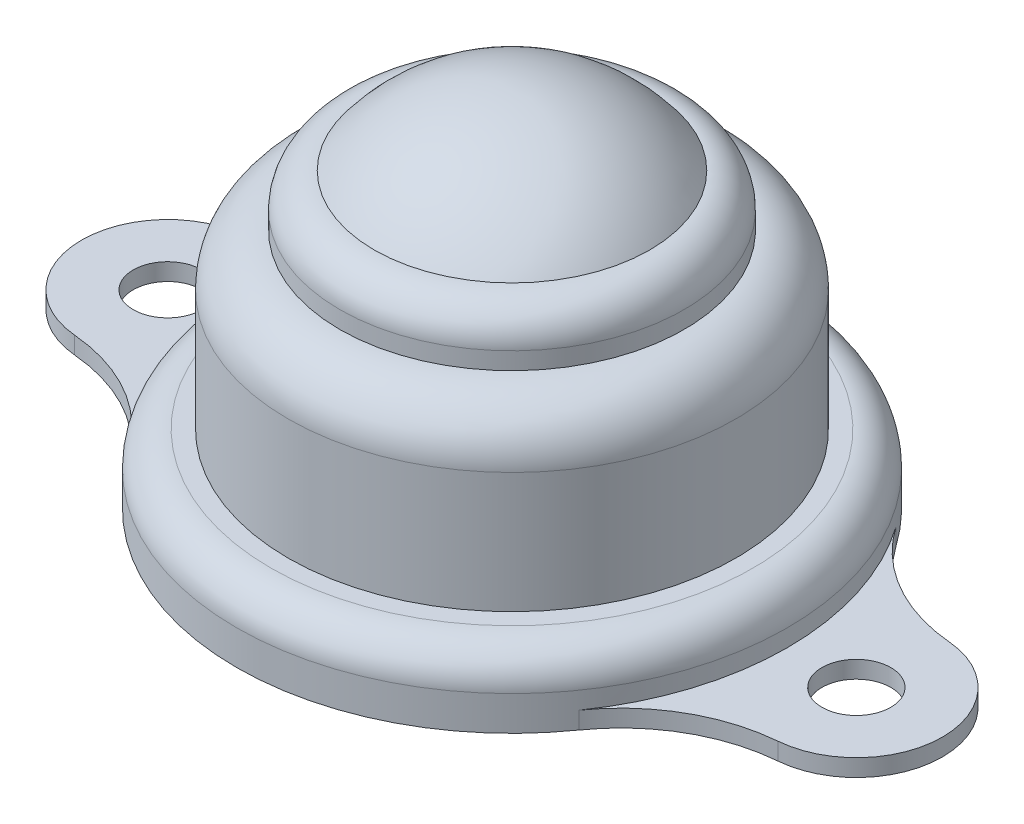
SolidWorks part; units mm, degrees
ref_plane "Front Plane" through (0, 0, 0) normal (0, 0, 1) x (1, 0, 0)
ref_plane "Top Plane" through (0, 0, 0) normal (0, 1, 0) x (1, 0, 0)
ref_plane "Right Plane" through (0, 0, 0) normal (1, 0, 0) x (0, 0, -1)
sketch "Sketch1" plane through (0, 0, 0) normal (0, 1, 0) x (1, 0, 0)
  line L0 (0, 0) -> (0, 10)
  circle A0 centre (-20, 0) radius 2
  circle A1 centre (20, 0) radius 2
  arc A2 (-20.425, 4.9819) -> (-20.425, -4.9819) centre (-20, 0) ccw
  arc A3 (20.425, -4.9819) -> (20.425, 4.9819) centre (20, 0) ccw
  circle A4 centre (0, 0) radius 10
  arc A5 (-13.0923, -9.1974) -> (13.0923, -9.1974) centre (0, 0) ccw
  arc A6 (13.0923, 9.1974) -> (-13.0923, 9.1974) centre (0, 0) ccw
  arc A7 (20.425, -4.9819) -> (13.0923, -9.1974) centre (21.275, -14.9457) ccw
  arc A8 (20.425, 4.9819) -> (13.0923, 9.1974) centre (21.275, 14.9457) cw
  arc A9 (-20.425, -4.9819) -> (-13.0923, -9.1974) centre (-21.275, -14.9457) cw
  arc A10 (-20.425, 4.9819) -> (-13.0923, 9.1974) centre (-21.275, 14.9457) ccw
  point P15 (15.775, 2.6738)
  dimension "D3" = 4
  dimension "D4" = 4
  dimension "D6" = 10
  dimension "D7" = 10
  dimension "D8" = 20
  dimension "D9" = 32
  dimension "D10" = 10
  dimension "D1" = 40
  dimension "D2" = 20
  dimension "D5" = 0
  dimension "D11" = 10
extrude "Boss-Extrude1" add sketch "Sketch1" along normal blind 1 contours A10 A2 A9 A5 A7 A3 A8 A6 A4 A1 A0 | A4 region at (-15.9952, 0, -5.7616) region at (-6.8711, 0, 6.8711)
sketch "Sketch2" plane through (0, 1, 0) normal (0, 1, 0) x (1, 0, 0)
  circle A0 centre (0, 0) radius 16
  circle A1 centre (0, 0) radius 13
  dimension "D1" = 32
  dimension "D2" = 26
extrude "Boss-Extrude2" add sketch "Sketch2" along normal blind 3 contours A0 | A1
fillet "Fillet2" radius 2 1 edges at (0, 4, 16)
ref_plane "Plane1" through (0, 4, 0) normal (0, 1, 0) x (1, 0, 0)
sketch "Sketch3" plane through (0, 4, 0) normal (0, 1, 0) x (1, 0, 0)
  circle A0 centre (0, 0) radius 13
  circle A1 centre (0, 0) radius 10
  dimension "D1" = 20
  dimension "D2" = 26
extrude "Boss-Extrude3" add sketch "Sketch3" along normal blind 10 separate body
sketch "Sketch4" plane through (0, 14, 0) normal (0, 1, 0) x (1, 0, 0)
  circle A0 centre (0, 0) radius 10
  circle A1 centre (0, 0) radius 8
  dimension "D1" = 20
  dimension "D2" = 16
extrude "Boss-Extrude4" add sketch "Sketch4" along normal blind 3 separate body
fillet "Fillet3" radius 2 1 edges at (0, 17, 10)
fillet "Fillet4" radius 3 1 edges at (0, 14, 13)
sketch "Sketch5" plane through (0, 0, 0) normal (0, 0, 1) x (1, 0, 0)
  line L0 (-13, 11) -> (-13, 4) construction
  line L2 (13, 4) -> (13, 11) construction
  line L3 (0, 1) -> (0, 21)
  arc A0 (0, 21) -> (0, 1) centre (0, 11) ccw
  dimension "D1" = 1
  dimension "D2" = 11
  dimension "D3" = 13
  dimension "D4" = 13
  dimension "D7" = 13
revolve "Revolve2" add sketch "Sketch5" angle 360 about L3
